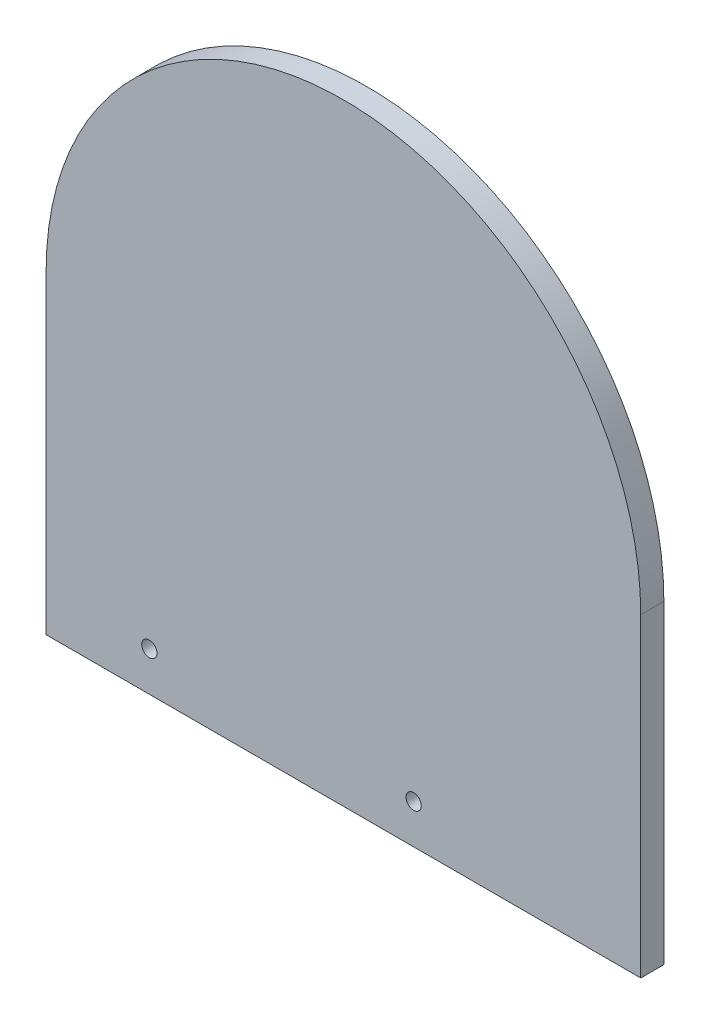
SolidWorks part; units mm, degrees
ref_plane "Front" through (0, 0, 0) normal (0, 0, 1) x (1, 0, 0)
ref_plane "Top" through (0, 0, 0) normal (0, 1, 0) x (1, 0, 0)
ref_plane "Right" through (0, 0, 0) normal (1, 0, 0) x (0, 0, -1)
ref_axis "side-side" through (80.9, 0, 0) along (-1, 0, 0)
ref_axis "up-down" through (0, 50, 0) along (0, -1, 0)
ref_axis "front-back" through (0, 0, -80.9) along (0, 0, 1)
sketch "Sketch1" plane through (0, 0, 0) normal (0, 0, 1) x (1, 0, 0)
  line L1 (-72, 0) -> (72, 0)
  line L2 (-72, 0) -> (-72, 76.2)
  line L3 (-72, 76.2) -> (72, 76.2) construction
  line L4 (72, 0) -> (72, 76.2)
  arc A0 (-72, 76.2) -> (72, 76.2) centre (0, 76.2) cw
  circle A1 centre (-47, 9.525) radius 1.85
  circle A2 centre (17, 9.525) radius 1.85
  point P10 (0, 0)
  dimension "D3" = 9.525
  dimension "D4" = 25
  dimension "D5" = 3.7
  dimension "D6" = 64
  dimension "D1" = 144
  dimension "D2" = 76.2
extrude "Boss-Extrude1" add sketch "Sketch1" along normal blind 5.6
